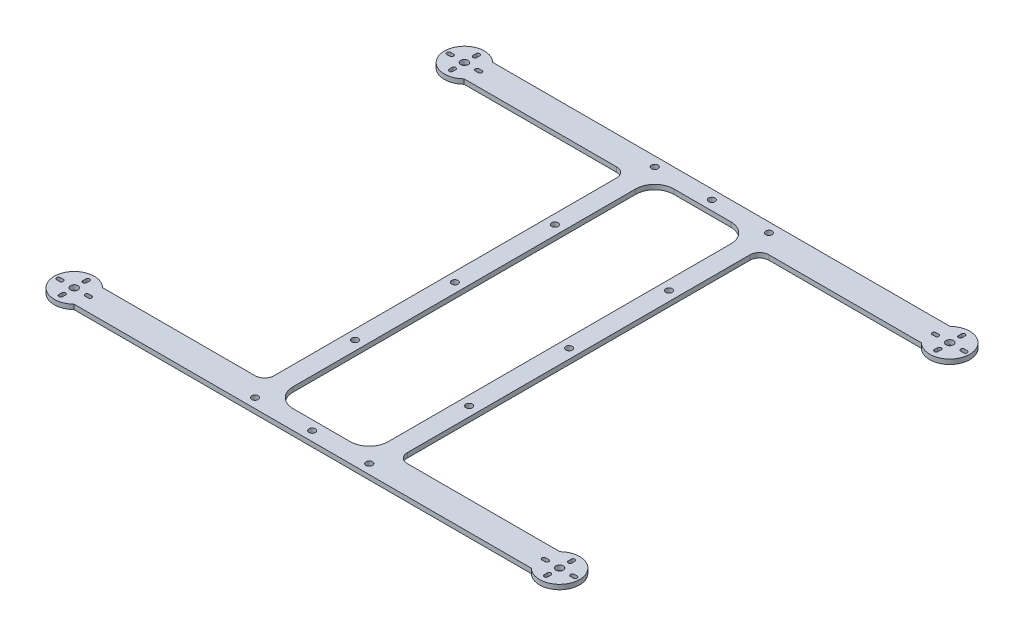
SolidWorks part; units mm, degrees
ref_plane "Front Plane" through (0, 0, 0) normal (0, 0, 1) x (1, 0, 0)
ref_plane "Top Plane" through (0, 0, 0) normal (0, 1, 0) x (1, 0, 0)
ref_plane "Right Plane" through (0, 0, 0) normal (1, 0, 0) x (0, 0, -1)
sketch "Sketch1" plane through (0, 0, 0) normal (0, 1, 0) x (1, 0, 0)
  line L1 (-44.45, 139.7) -> (44.45, 139.7)
  line L2 (-44.45, 120.65) -> (-44.45, -120.65)
  line L3 (-44.45, -139.7) -> (44.45, -139.7)
  line L4 (44.45, 120.65) -> (44.45, -120.65)
  line L5 (44.45, 139.7) -> (161.925, 139.7)
  line L7 (44.45, 120.65) -> (161.925, 120.65)
  line L8 (161.925, 139.7) -> (161.925, 120.65)
  line L14 (0, 0) -> (0, 187.5455) construction
  line L17 (0, 0) -> (-239.6804, 0) construction
  line L21 (0, 0) -> (44.45, 0) construction
  line L22 (-44.45, 120.65) -> (-161.925, 120.65)
  line L23 (-44.45, 139.7) -> (-161.925, 139.7)
  line L24 (-161.925, 139.7) -> (-161.925, 120.65)
  line L37 (-31.75, 127) -> (31.75, 127)
  line L40 (-31.75, 127) -> (-31.75, -127)
  line L43 (-31.75, -127) -> (31.75, -127)
  line L46 (31.75, 127) -> (31.75, -127)
  line L49 (44.45, -120.65) -> (161.925, -120.65)
  line L50 (44.45, -139.7) -> (161.925, -139.7)
  line L51 (161.925, -139.7) -> (161.925, -120.65)
  line L88 (-161.925, -139.7) -> (-161.925, -120.65)
  line L89 (-44.45, -139.7) -> (-161.925, -139.7)
  line L90 (-44.45, -120.65) -> (-161.925, -120.65)
  point P4 (0, 139.7)
  point P6 (-44.45, 0)
  dimension "D4" = 117.475
  dimension "D1" = 279.4
  dimension "D2" = 88.9
  dimension "D3" = 19.05
  dimension "D6" = 12.7
  dimension "D7" = 12.7
  dimension "D8" = 12.7
  dimension "D10" = 117.475
  dimension "D12" = 12.7
  dimension "D18" = 19.05
extrude "Boss-Extrude1" add sketch "Sketch1" along normal blind 3.175
sketch "Sketch4" plane through (0, 3.175, 0) normal (0, 1, 0) x (1, 0, 0)
  line L0 (161.925, 120.65) -> (161.925, 139.7) construction
  line L1 (-161.925, 139.7) -> (-161.925, 120.65) construction
  line L2 (-161.925, -120.65) -> (-161.925, -139.7) construction
  line L3 (161.925, -139.7) -> (161.925, -120.65) construction
  circle A0 centre (161.925, 130.175) radius 13.335
  circle A1 centre (-161.925, 130.175) radius 13.335
  circle A2 centre (-161.925, -130.175) radius 13.335
  circle A3 centre (161.925, -130.175) radius 13.335
  point P18 (161.925, -130.175)
extrude "Boss-Extrude4" add sketch "Sketch4" against normal up to surface (3.175 mm away) up to face at (0, 0, 0)
sketch "Sketch5" plane through (0, 3.175, 0) normal (0, 1, 0) x (1, 0, 0)
  line L0 (151.425, 130.175) -> (153.425, 130.175) construction
  line L1 (151.425, 131.425) -> (153.425, 131.425)
  line L2 (151.425, 128.925) -> (153.425, 128.925)
  line L3 (161.925, 130.175) -> (161.925, 143.51) construction
  line L4 (172.425, 130.175) -> (170.425, 130.175) construction
  line L5 (172.425, 131.425) -> (170.425, 131.425)
  line L6 (172.425, 128.925) -> (170.425, 128.925)
  line L7 (161.925, 139.175) -> (161.925, 137.175) construction
  line L8 (163.175, 139.175) -> (163.175, 137.175)
  line L9 (160.675, 139.175) -> (160.675, 137.175)
  line L10 (161.925, 130.175) -> (175.26, 130.175) construction
  line L11 (161.925, 121.175) -> (161.925, 123.175) construction
  line L12 (163.175, 121.175) -> (163.175, 123.175)
  line L13 (160.675, 121.175) -> (160.675, 123.175)
  line L14 (0, 0) -> (0, 263.0018) construction
  line L15 (0, 0) -> (558.7896, 0) construction
  line L16 (-151.425, 130.175) -> (-153.425, 130.175) construction
  line L17 (-151.425, 131.425) -> (-153.425, 131.425)
  line L18 (-151.425, 128.925) -> (-153.425, 128.925)
  line L19 (-172.425, 130.175) -> (-170.425, 130.175) construction
  line L20 (-172.425, 131.425) -> (-170.425, 131.425)
  line L21 (-172.425, 128.925) -> (-170.425, 128.925)
  line L22 (-161.925, 139.175) -> (-161.925, 137.175) construction
  line L23 (-163.175, 139.175) -> (-163.175, 137.175)
  line L24 (-160.675, 139.175) -> (-160.675, 137.175)
  line L25 (-161.925, 121.175) -> (-161.925, 123.175) construction
  line L26 (-163.175, 121.175) -> (-163.175, 123.175)
  line L27 (-160.675, 121.175) -> (-160.675, 123.175)
  line L28 (-161.925, 130.175) -> (-175.26, 130.175) construction
  line L29 (-161.925, 130.175) -> (-161.925, 143.51) construction
  line L30 (151.425, -130.175) -> (153.425, -130.175) construction
  line L31 (151.425, -131.425) -> (153.425, -131.425)
  line L32 (151.425, -128.925) -> (153.425, -128.925)
  line L33 (161.925, -139.175) -> (161.925, -137.175) construction
  line L34 (163.175, -139.175) -> (163.175, -137.175)
  line L35 (160.675, -139.175) -> (160.675, -137.175)
  line L36 (172.425, -130.175) -> (170.425, -130.175) construction
  line L37 (172.425, -131.425) -> (170.425, -131.425)
  line L38 (172.425, -128.925) -> (170.425, -128.925)
  line L39 (161.925, -121.175) -> (161.925, -123.175) construction
  line L40 (163.175, -121.175) -> (163.175, -123.175)
  line L41 (160.675, -121.175) -> (160.675, -123.175)
  line L42 (161.925, -130.175) -> (175.26, -130.175) construction
  line L43 (161.925, -130.175) -> (161.925, -143.51) construction
  line L44 (-161.925, -130.175) -> (-161.925, -143.51) construction
  line L45 (-161.925, -130.175) -> (-175.26, -130.175) construction
  line L46 (-161.925, -121.175) -> (-161.925, -123.175) construction
  line L47 (-163.175, -121.175) -> (-163.175, -123.175)
  line L48 (-160.675, -121.175) -> (-160.675, -123.175)
  line L49 (-161.925, -139.175) -> (-161.925, -137.175) construction
  line L50 (-163.175, -139.175) -> (-163.175, -137.175)
  line L51 (-160.675, -139.175) -> (-160.675, -137.175)
  line L52 (-172.425, -130.175) -> (-170.425, -130.175) construction
  line L53 (-172.425, -131.425) -> (-170.425, -131.425)
  line L54 (-172.425, -128.925) -> (-170.425, -128.925)
  line L55 (-151.425, -130.175) -> (-153.425, -130.175) construction
  line L56 (-151.425, -131.425) -> (-153.425, -131.425)
  line L57 (-151.425, -128.925) -> (-153.425, -128.925)
  circle A0 centre (161.925, 130.175) radius 2.5
  arc A1 (151.425, 131.425) -> (151.425, 128.925) centre (151.425, 130.175) ccw
  arc A2 (153.425, 128.925) -> (153.425, 131.425) centre (153.425, 130.175) ccw
  arc A3 (152.5924, 120.65) -> (152.5924, 139.7) centre (161.925, 130.175) ccw construction
  arc A4 (172.425, 131.425) -> (172.425, 128.925) centre (172.425, 130.175) cw
  arc A5 (170.425, 128.925) -> (170.425, 131.425) centre (170.425, 130.175) cw
  arc A6 (163.175, 139.175) -> (160.675, 139.175) centre (161.925, 139.175) ccw
  arc A7 (160.675, 137.175) -> (163.175, 137.175) centre (161.925, 137.175) ccw
  arc A8 (163.175, 121.175) -> (160.675, 121.175) centre (161.925, 121.175) cw
  arc A9 (160.675, 123.175) -> (163.175, 123.175) centre (161.925, 123.175) cw
  arc A10 (-151.425, 131.425) -> (-151.425, 128.925) centre (-151.425, 130.175) cw
  arc A11 (-153.425, 128.925) -> (-153.425, 131.425) centre (-153.425, 130.175) cw
  arc A12 (-172.425, 131.425) -> (-172.425, 128.925) centre (-172.425, 130.175) ccw
  arc A13 (-170.425, 128.925) -> (-170.425, 131.425) centre (-170.425, 130.175) ccw
  arc A14 (-163.175, 139.175) -> (-160.675, 139.175) centre (-161.925, 139.175) cw
  arc A15 (-160.675, 137.175) -> (-163.175, 137.175) centre (-161.925, 137.175) cw
  arc A16 (-163.175, 121.175) -> (-160.675, 121.175) centre (-161.925, 121.175) ccw
  arc A17 (-160.675, 123.175) -> (-163.175, 123.175) centre (-161.925, 123.175) ccw
  circle A18 centre (-161.925, 130.175) radius 2.5
  arc A19 (151.425, -131.425) -> (151.425, -128.925) centre (151.425, -130.175) cw
  arc A20 (153.425, -128.925) -> (153.425, -131.425) centre (153.425, -130.175) cw
  arc A21 (163.175, -139.175) -> (160.675, -139.175) centre (161.925, -139.175) cw
  arc A22 (160.675, -137.175) -> (163.175, -137.175) centre (161.925, -137.175) cw
  arc A23 (172.425, -131.425) -> (172.425, -128.925) centre (172.425, -130.175) ccw
  arc A24 (170.425, -128.925) -> (170.425, -131.425) centre (170.425, -130.175) ccw
  arc A25 (163.175, -121.175) -> (160.675, -121.175) centre (161.925, -121.175) ccw
  arc A26 (160.675, -123.175) -> (163.175, -123.175) centre (161.925, -123.175) ccw
  circle A27 centre (161.925, -130.175) radius 2.5
  circle A28 centre (-161.925, -130.175) radius 2.5
  arc A29 (-163.175, -121.175) -> (-160.675, -121.175) centre (-161.925, -121.175) cw
  arc A30 (-160.675, -123.175) -> (-163.175, -123.175) centre (-161.925, -123.175) cw
  arc A31 (-163.175, -139.175) -> (-160.675, -139.175) centre (-161.925, -139.175) ccw
  arc A32 (-160.675, -137.175) -> (-163.175, -137.175) centre (-161.925, -137.175) ccw
  arc A33 (-172.425, -131.425) -> (-172.425, -128.925) centre (-172.425, -130.175) cw
  arc A34 (-170.425, -128.925) -> (-170.425, -131.425) centre (-170.425, -130.175) cw
  arc A35 (-151.425, -131.425) -> (-151.425, -128.925) centre (-151.425, -130.175) ccw
  arc A36 (-153.425, -128.925) -> (-153.425, -131.425) centre (-153.425, -130.175) ccw
  point P5 (152.425, 130.175)
  point P16 (171.425, 130.175)
  point P23 (161.925, 138.175)
  point P31 (161.925, 122.175)
  point P42 (-152.425, 130.175)
  point P49 (-171.425, 130.175)
  point P56 (-161.925, 138.175)
  point P63 (-161.925, 122.175)
  point P74 (152.425, -130.175)
  point P81 (161.925, -138.175)
  point P88 (171.425, -130.175)
  point P95 (161.925, -122.175)
  point P110 (-161.925, -122.175)
  point P117 (-161.925, -138.175)
  point P124 (-171.425, -130.175)
  point P131 (-152.425, -130.175)
  dimension "D1" = 5
  dimension "D2" = 2.5
  dimension "D3" = 2
  dimension "D4" = 19
  dimension "D5" = 2.5
  dimension "D6" = 2
  dimension "D7" = 16
extrude "Motor Holes" cut sketch "Sketch5" against normal through all
sketch "Sketch7" plane through (0, 3.175, 0) normal (0, 1, 0) x (1, 0, 0)
  line L0 (152.5924, 139.7) -> (-152.5924, 139.7) construction
  line L1 (-44.45, 120.65) -> (-44.45, -120.65) construction
  line L2 (0, 0) -> (0, 246.0772) construction
  line L3 (0, 0) -> (301.4392, 0) construction
  circle A0 centre (-38.1, 133.35) radius 2.159
  circle A1 centre (-38.1, 66.675) radius 2.159
  circle A2 centre (-38.1, 0) radius 2.159
  circle A3 centre (-38.1, -66.675) radius 2.159
  circle A5 centre (-38.1, -133.35) radius 2.159
  circle A6 centre (38.1, -133.35) radius 2.159
  circle A7 centre (38.1, -66.675) radius 2.159
  circle A8 centre (38.1, 0) radius 2.159
  circle A9 centre (38.1, 66.675) radius 2.159
  circle A10 centre (38.1, 133.35) radius 2.159
  circle A11 centre (0, 133.35) radius 2.159
  circle A12 centre (0, -133.35) radius 2.159
  dimension "D1" = 4.318
  dimension "D2" = 6.35
  dimension "D3" = 6.35
  dimension "D4" = 66.675
  dimension "D5" = 66.675
  dimension "D6" = 66.675
  dimension "D7" = 66.675
extrude "Cut-Extrude2" cut sketch "Sketch7" against normal through all
fillet "Fillet1" radius 12.7 4 edges at (31.75, 1.5875, 127) (-31.75, 1.5875, 127) (-31.75, 1.5875, -127) (31.75, 1.5875, -127)
fillet "Fillet2" radius 6.35 4 edges at (-44.45, 1.5875, 120.65) (-44.45, 1.5875, -120.65) (44.45, 1.5875, -120.65) (44.45, 1.5875, 120.65)
